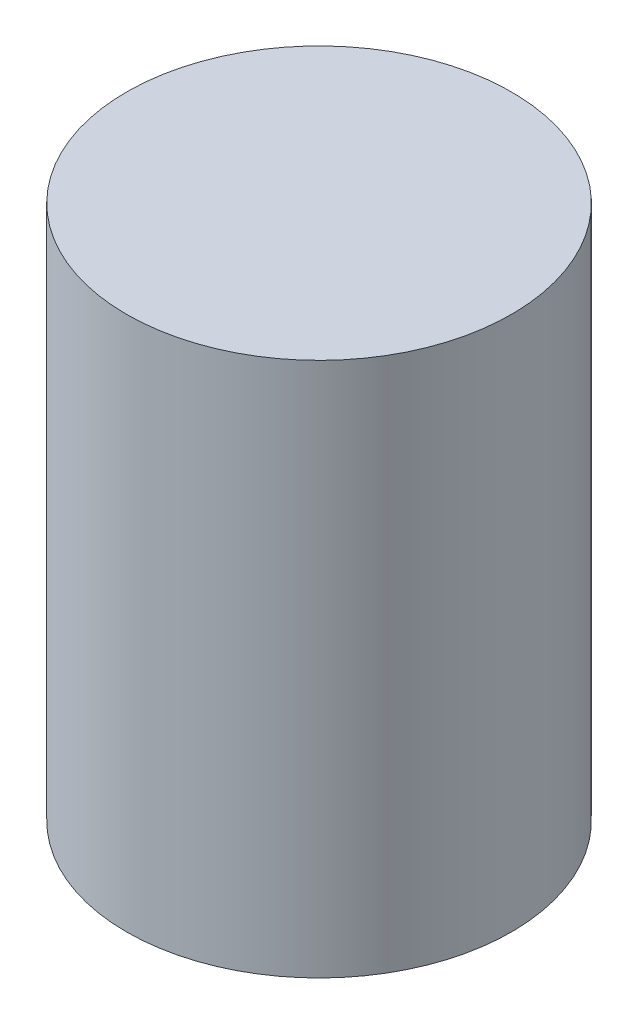
SolidWorks part; units mm, degrees
ref_plane "Front Plane" through (0, 0, 0) normal (0, 0, 1) x (1, 0, 0)
ref_plane "Top Plane" through (0, 0, 0) normal (0, 1, 0) x (1, 0, 0)
ref_plane "Right Plane" through (0, 0, 0) normal (1, 0, 0) x (0, 0, -1)
sketch "Sketch1" plane through (0, 0, 0) normal (0, 1, 0) x (1, 0, 0)
  circle A0 centre (0, 0) radius 18
  dimension "D1" = 36
extrude "Boss-Extrude1" add sketch "Sketch1" along normal blind 50
